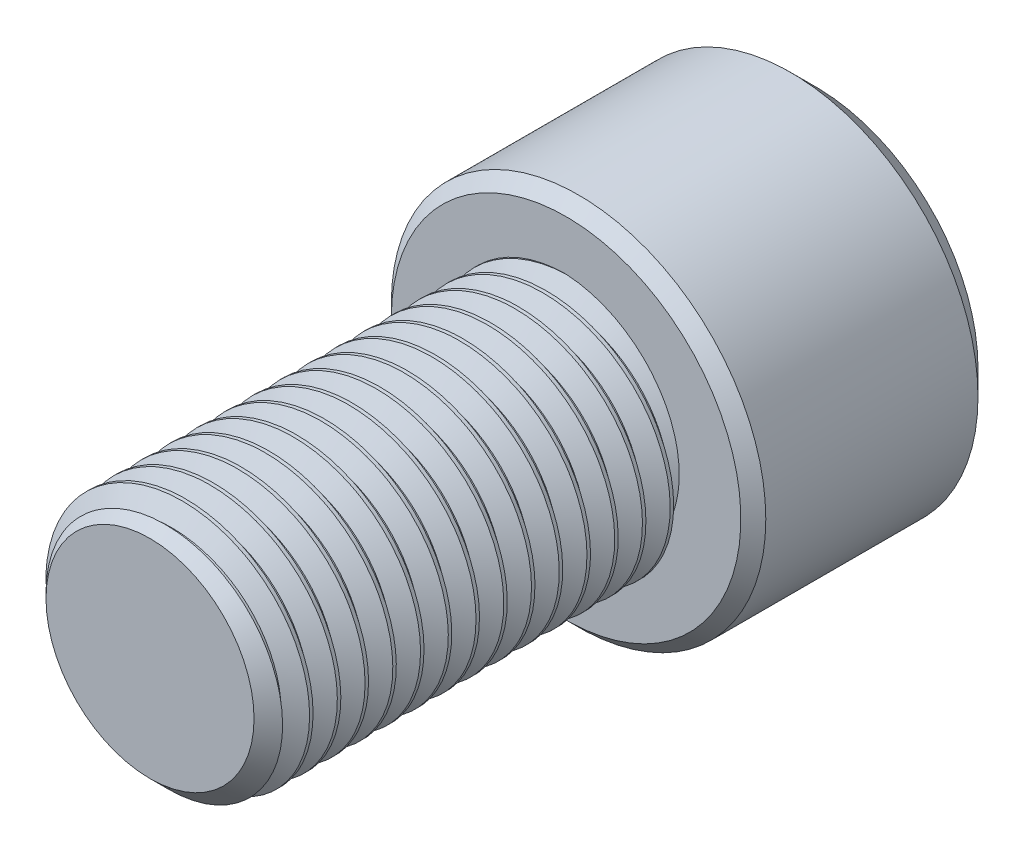
SolidWorks part; units mm, degrees
ref_plane "Front Plane" through (0, 0, 0) normal (0, 0, 1) x (1, 0, 0)
ref_plane "Top Plane" through (0, 0, 0) normal (0, 1, 0) x (1, 0, 0)
ref_plane "Right Plane" through (0, 0, 0) normal (1, 0, 0) x (0, 0, -1)
sketch "Sketch1" plane through (0, 0, 0) normal (0, 0, 1) x (1, 0, 0)
  line L0 (0, 4.7625) -> (0, -4.7625) construction
  circle A0 centre (0, 0) radius 4.7625
  dimension "OD" = 9.525
extrude "Extrude1" add sketch "Sketch1" against normal blind 15.875
sketch "Sketch2" plane through (0, 0, 0) normal (0, 0, 1) x (1, 0, 0)
  circle A0 centre (0, 0) radius 4.7625 construction
  circle A1 centre (0, 0) radius 4.7625
curve "Helix/Spiral1" pitch 1.0583 height 16.9333 turns 16 parameters "pitch"=1.0583
chamfer "Chamfer3" distance 0.7937 angle 45 1 edges at (4.7625, 0, 0)
sketch "Sketch3" plane through (0, 0, 0) normal (1, 0, 0) x (0, 0, -1)
  line L0 (-0.926, 4.7625) -> (-0.5292, 4.0751)
  line L1 (-0.5292, 4.0751) -> (-0.3969, 4.0751)
  line L2 (-0.3969, 4.0751) -> (0, 4.7625)
  line L3 (-0.926, 4.7625) -> (0, 4.7625)
  line L4 (-0.463, 4.7625) -> (-0.463, 4.0751) construction
  line L5 (-0.7276, 4.4188) -> (-0.1984, 4.4188) construction
  line L6 (0, 4.7625) -> (0, -4.7625) construction
  dimension "D1" = 0.1323
  dimension "D2" = 0.5292
  dimension "D3" = 60
sweep "Cut-Sweep1" cut profiles "Sketch3" path "Helix/Spiral1"
sketch "Sketch6" plane through (0, 0, -15.875) normal (0, 0, -1) x (-1, 0, 0)
  circle A0 centre (0, 0) radius 7.1438
  dimension "head dia" = 14.2875
extrude "Extrude2" add sketch "Sketch6" along normal blind 9.525
sketch "Sketch7" plane through (0, 0, -25.4) normal (0, 0, -1) x (-1, 0, 0)
  line L1 (0, 4.5827) -> (-3.9688, 2.2914)
  line L2 (-3.9688, 2.2914) -> (-3.9688, -2.2914)
  line L3 (-3.9688, -2.2914) -> (0, -4.5827)
  line L4 (0, -4.5827) -> (3.9688, -2.2914)
  line L5 (3.9688, -2.2914) -> (3.9687, 2.2914)
  line L6 (3.9687, 2.2914) -> (0, 4.5827)
  circle A0 centre (0, 0) radius 3.9688 construction
  dimension "hex dia" = 7.9375
extrude "Cut-Extrude1" cut sketch "Sketch7" against normal blind 5.9531
sketch "Sketch8" plane through (0, 0, -25.4) normal (0, 0, -1) x (-1, 0, 0)
  circle A0 centre (0, 0) radius 4.5827
extrude "Cut-Extrude2" cut sketch "Sketch8" against normal blind 0.9525 draft 45
chamfer "Chamfer1" distance 0.9525 angle 45 1 edges at (-7.1438, 0, -25.4)
chamfer "Chamfer2" distance 0.4763 angle 45 1 edges at (-7.1438, 0, -15.875)
sketch "Sketch9" plane through (0, 0, 0) normal (1, 0, 0) x (0, 0, -1)
  line L0 (0, 4.7625) -> (0, -4.7625) construction
  line L1 (5.8208, 4.7625) -> (5.8208, -4.7625) construction
  line L2 (15.875, 7.1437) -> (15.875, -7.1438) construction
  line L3 (25.4, 7.1437) -> (25.4, -7.1438) construction
  line L4 (25.4, 0) -> (0, 0) construction
  dimension "D1" = 5.8208
  dimension "D2" = 9.525
  dimension "D3" = 14.2875
  dimension "D4" = 15.875
equation "\"D3@Helix/Spiral1\" = \"screw length@Extrude1\"+\"pitch@Helix/Spiral1\""
equation "\"D1@Sketch3\" = \"pitch@Helix/Spiral1\"*.125"
equation "\"D2@Sketch3\" = \"pitch@Helix/Spiral1\"*.5"
equation "\"D1@Cut-Extrude1\" = \"hex dia@Sketch7\"*.75"
equation "\"D1@Chamfer1\" = \"head depth@Extrude2\"/10"
equation "\"D1@Sketch9\" = \"pitch@Helix/Spiral1\"*5.5"
equation "\"D1@Chamfer2\" = \"D1@Chamfer1\"/2"
equation "\"D1@Cut-Extrude2\" = \"D1@Chamfer2\"*2"
equation "\"D1@Chamfer3\" = \"pitch@Helix/Spiral1\"*.750"
equation "\"D2@Sketch9\" = \"head depth@Extrude2\""
equation "\"D3@Sketch9\" = \"head dia@Sketch6\""
equation "\"D4@Sketch9\" = \"screw length@Extrude1\""
